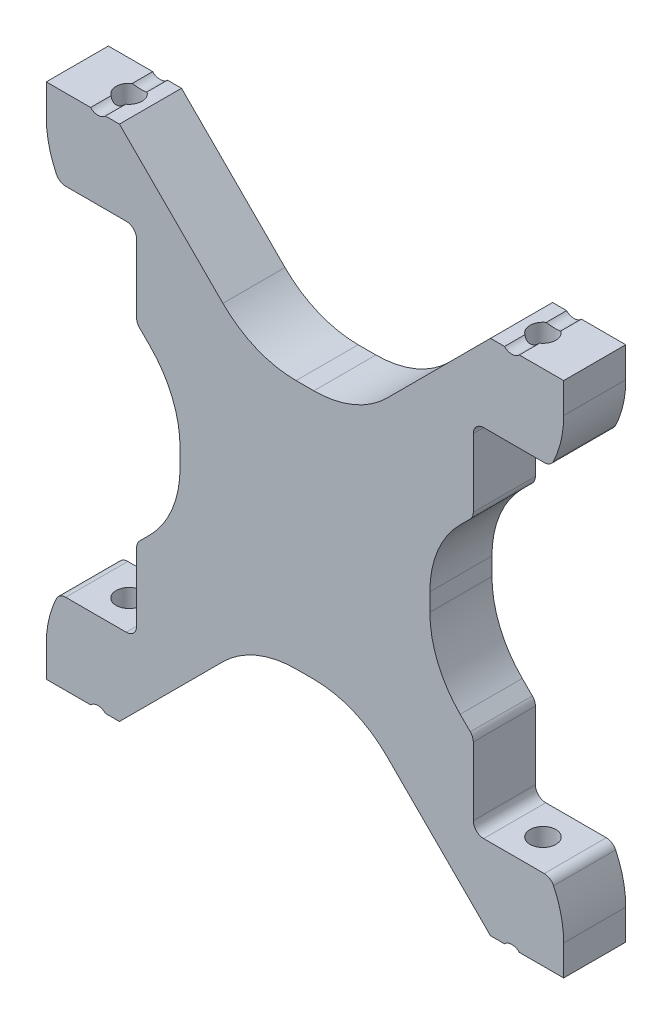
SolidWorks part; units mm, degrees
ref_plane "正面" through (0, 0, 0) normal (0, 0, 1) x (1, 0, 0)
ref_plane "平面" through (0, 0, 0) normal (0, 1, 0) x (1, 0, 0)
ref_plane "右側面" through (0, 0, 0) normal (1, 0, 0) x (0, 0, -1)
sketch "ｽｹｯﾁ1" plane through (0, 0, 0) normal (0, 0, 1) x (1, 0, 0)
  line L0 (-32.0711, 25) -> (-12.0711, 5)
  line L1 (-12.0711, -5) -> (-32.0711, -25)
  line L2 (-32.0711, -25) -> (-17.9289, -25)
  line L3 (-17.9289, -25) -> (-5, -12.0711)
  line L4 (5, -12.0711) -> (17.9289, -25)
  line L5 (17.9289, -25) -> (32.0711, -25)
  line L6 (32.0711, -25) -> (12.0711, -5)
  line L7 (12.0711, 5) -> (32.0711, 25)
  line L8 (32.0711, 25) -> (17.9289, 25)
  line L9 (17.9289, 25) -> (5, 12.0711)
  line L10 (-5, 12.0711) -> (-17.9289, 25)
  line L11 (-17.9289, 25) -> (-32.0711, 25)
  line L12 (-12.0711, 5) -> (-12.0711, -5)
  line L13 (-5, -12.0711) -> (5, -12.0711)
  line L14 (12.0711, -5) -> (12.0711, 5)
  line L15 (5, 12.0711) -> (-5, 12.0711)
  line L16 (12.0711, 5) -> (-12.0711, -5) construction
  line L17 (-12.0711, 5) -> (12.0711, -5) construction
  line L18 (-12.0711, 5) -> (12.0711, 5) construction
  line L19 (5, 12.0711) -> (-5, -12.0711) construction
  line L20 (-5, 12.0711) -> (5, -12.0711) construction
  point P1 (0, 0)
  point P11 (0, 0)
  dimension "D1" = 10
  dimension "D2" = 135
  dimension "D3" = 10
  dimension "D4" = 10
  dimension "D5" = 50
  dimension "D6" = 135
extrude "ﾎﾞｽ - 押し出し1" add sketch "ｽｹｯﾁ1" along normal blind 6
sketch "ｽｹｯﾁ2" plane through (0, 0, 6) normal (0, 0, 1) x (1, 0, 0)
  line L0 (0, 0) -> (0, 38.1314) construction
  line L1 (-17.9289, 25) -> (-32.0711, 25) construction
  line L2 (-20.7141, 25) -> (-19.2859, 25)
  line L3 (20.7141, 25) -> (19.2859, 25)
  arc A0 (-20.7141, 25) -> (-19.2859, 25) centre (-20, 25.7) ccw
  arc A1 (20.7141, 25) -> (19.2859, 25) centre (20, 25.7) cw
  dimension "D1" = 20
  dimension "D2" = 2
  dimension "D3" = 0.7
extrude "ｶｯﾄ - 押し出し1" cut sketch "ｽｹｯﾁ2" against normal through all
fillet "ﾌｨﾚｯﾄ1" radius 2 2 edges at (32.0711, 25, 3) (-32.0711, 25, 3)
ref_plane "平面1" through (0, 0, 0) normal (0, 1, 0) x (1, 0, 0)
mirror "ﾐﾗｰ3" about plane through (0, 0, 0) normal (0, 1, 0) of "ｶｯﾄ - 押し出し1", "ﾌｨﾚｯﾄ1"
sketch "ｽｹｯﾁ3" plane through (0, 25, 0) normal (0, 1, 0) x (1, 0, 0)
  line L0 (-29.2426, -3) -> (29.2426, -3) construction
  line L1 (-29.2426, 0) -> (-29.2426, -6) construction
  line L2 (29.2426, -6) -> (29.2426, 0) construction
  line L3 (-20, 0) -> (-20, -6) construction
  line L4 (-19.2859, 0) -> (-20.7141, 0) construction
  line L5 (-20.7141, -6) -> (-19.2859, -6) construction
  line L6 (20, 0) -> (20, -6) construction
  line L7 (20.7141, 0) -> (19.2859, 0) construction
  line L8 (19.2859, -6) -> (20.7141, -6) construction
  circle A0 centre (-20, -3) radius 1.25
  circle A1 centre (20, -3) radius 1.25
  dimension "D1" = 2.5
extrude "ｶｯﾄ - 押し出し2" cut sketch "ｽｹｯﾁ3" against normal through all
sketch "ｽｹｯﾁ4" plane through (0, 0, 6) normal (0, 0, 1) x (1, 0, 0)
  line L0 (27.2426, 25) -> (20.7141, 25) construction
  line L2 (-25, -25) -> (-25, 25)
  line L4 (25, -25) -> (25, 25)
  line L5 (-25, -25) -> (25, 25) construction
  line L6 (-25, 25) -> (25, -25) construction
  line L7 (-27.2426, -25) -> (-20.7141, -25) construction
  line L8 (29.2426, 25) -> (25, 25)
  line L9 (29.2426, 25) -> (29.2426, -25)
  line L10 (29.2426, -25) -> (25, -25)
  line L11 (-29.2426, 25) -> (-29.2426, -25)
  line L12 (29.2426, 25) -> (-29.2426, -25) construction
  line L13 (29.2426, -25) -> (-29.2426, 25) construction
  line L14 (-25, -25) -> (-29.2426, -25)
  line L15 (-25, 25) -> (-29.2426, 25)
  arc A0 (-28.6569, -21.5858) -> (-27.2426, -25) centre (-27.2426, -23) ccw construction
  point P0 (0, 0)
  point P8 (0, 0)
extrude "ｶｯﾄ - 押し出し3" cut sketch "ｽｹｯﾁ4" against normal through all
fillet "ﾌｨﾚｯﾄ2" radius 10 12 edges at (25, 17.9289, 3) (12.0711, 5, 3) (12.0711, -5, 3) (25, -17.9289, 3) (5, -12.0711, 3) (-5, -12.0711, 3) (-25, -17.9289, 3) (-12.0711, -5, 3) (-12.0711, 5, 3) (-25, 17.9289, 3) (5, 12.0711, 3) (-5, 12.0711, 3)
sketch "ｽｹｯﾁ5" plane through (0, 0, 6) normal (0, 0, 1) x (1, 0, 0)
  line L0 (-20, 25.7) -> (-20, 12.9289) construction
  line L1 (-22.0711, 15) -> (-15, 7.9289) construction
  line L2 (0, 12.0711) -> (0, -12.0711) construction
  line L3 (-23.7318, 17.1971) -> (-16.2682, 17.1971)
  line L4 (-23.7318, 17.1971) -> (-23.7318, 9.1971)
  line L5 (-23.7318, 9.1971) -> (-16.2682, 9.1971)
  line L6 (-16.2682, 17.1971) -> (-16.2682, 9.1971)
  line L7 (-23.7318, 17.1971) -> (-16.2682, 9.1971) construction
  line L8 (-23.7318, 9.1971) -> (-16.2682, 17.1971) construction
  line L9 (0.8579, 12.0711) -> (-0.8579, 12.0711) construction
  line L10 (-0.8579, -12.0711) -> (0.8579, -12.0711) construction
  line L11 (-12.0711, 0) -> (12.0711, 0) construction
  line L12 (-12.0711, 0.8579) -> (-12.0711, -0.8579) construction
  line L13 (12.0711, -0.8579) -> (12.0711, 0.8579) construction
  line L14 (23.7318, 9.1971) -> (16.2682, 9.1971)
  line L15 (16.2682, 17.1971) -> (16.2682, 9.1971)
  line L16 (23.7318, 17.1971) -> (16.2682, 17.1971)
  line L17 (23.7318, 17.1971) -> (23.7318, 9.1971)
  line L18 (-23.7318, -9.1971) -> (-16.2682, -9.1971)
  line L19 (-16.2682, -17.1971) -> (-16.2682, -9.1971)
  line L20 (-23.7318, -17.1971) -> (-16.2682, -17.1971)
  line L21 (-23.7318, -17.1971) -> (-23.7318, -9.1971)
  line L22 (23.7318, -17.1971) -> (23.7318, -9.1971)
  line L23 (23.7318, -17.1971) -> (16.2682, -17.1971)
  line L24 (16.2682, -17.1971) -> (16.2682, -9.1971)
  line L25 (23.7318, -9.1971) -> (16.2682, -9.1971)
  arc A0 (-25, 22.0711) -> (-22.0711, 15) centre (-15, 22.0711) ccw construction
  point P5 (-20, 13.1971)
  dimension "D1" = 8
extrude "ｶｯﾄ - 押し出し4" cut sketch "ｽｹｯﾁ5" against normal through all
fillet "ﾌｨﾚｯﾄ3" radius 1 12 edges at (-23.7318, -17.1971, 3) (-16.2682, -17.1971, 3) (-16.2682, -9.1971, 3) (23.7318, -17.1971, 3) (16.2682, -9.1971, 3) (16.2682, -17.1971, 3) (16.2682, 9.1971, 3) (23.7318, 17.1971, 3) (16.2682, 17.1971, 3) (-16.2682, 9.1971, 3) (-23.7318, 17.1971, 3) (-16.2682, 17.1971, 3)
